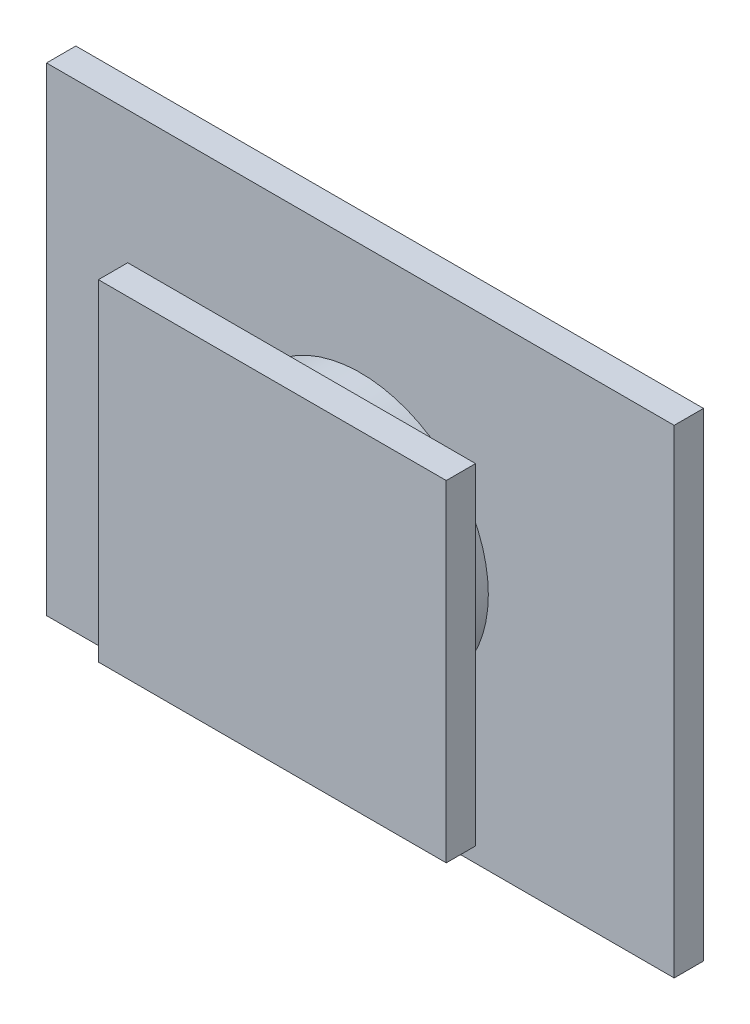
SolidWorks part; units mm, degrees
ref_plane "Front Plane" through (0, 0, 0) normal (0, 0, 1) x (1, 0, 0)
ref_plane "Top Plane" through (0, 0, 0) normal (0, 1, 0) x (1, 0, 0)
ref_plane "Right Plane" through (0, 0, 0) normal (1, 0, 0) x (0, 0, -1)
sketch "Sketch1" plane through (0, 0, 0) normal (0, 0, 1) x (1, 0, 0)
  circle A0 centre (0, 0) radius 43.6326
extrude "Boss-Extrude1" add sketch "Sketch1" along normal blind 10
sketch "Sketch2" plane through (0, 0, 10) normal (0, 0, 1) x (1, 0, 0)
  circle A0 centre (0, 0) radius 18.0827
extrude "Cut-Extrude1" cut sketch "Sketch2" against normal up to surface (10 mm away) up to face at (43.6326, 0, 0)
sketch "Sketch3" plane through (0, 0, 10) normal (0, 0, 1) x (1, 0, 0)
  circle A0 centre (0, 0) radius 26.6286
extrude "Boss-Extrude2" add sketch "Sketch3" along normal blind 10
sketch "Sketch4" plane through (0, 0, 20) normal (0, 0, 1) x (1, 0, 0)
  line L1 (-59.2866, 56.4405) -> (59.2866, 56.4405)
  line L2 (-59.2866, 56.4405) -> (-59.2866, -56.4405)
  line L3 (-59.2866, -56.4405) -> (59.2866, -56.4405)
  line L4 (59.2866, 56.4405) -> (59.2866, -56.4405)
  line L5 (-59.2866, 56.4405) -> (59.2866, -56.4405) construction
  line L6 (-59.2866, -56.4405) -> (59.2866, 56.4405) construction
  point P0 (0, 0)
extrude "Boss-Extrude3" add sketch "Sketch4" along normal blind 10
sketch "Sketch5" plane through (0, 0, 0) normal (0, 0, -1) x (-1, 0, 0)
  line L1 (-106.9769, 81.5772) -> (106.9769, 81.5772)
  line L2 (-106.9769, 81.5772) -> (-106.9769, -81.5772)
  line L3 (-106.9769, -81.5772) -> (106.9769, -81.5772)
  line L4 (106.9769, 81.5772) -> (106.9769, -81.5772)
  line L5 (-106.9769, 81.5772) -> (106.9769, -81.5772) construction
  line L6 (-106.9769, -81.5772) -> (106.9769, 81.5772) construction
  point P0 (0, 0)
extrude "Boss-Extrude4" add sketch "Sketch5" along normal blind 10
